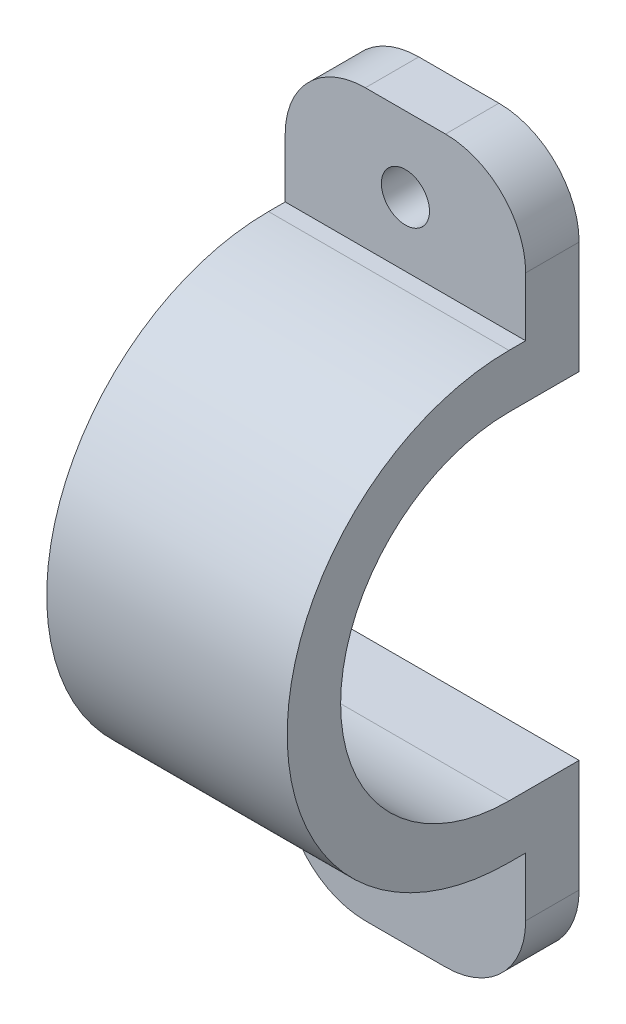
SolidWorks part; units mm, degrees
ref_plane "Top" through (0, 0, 0) normal (0, 0, 1) x (1, 0, 0)
ref_plane "Front" through (0, 0, 0) normal (0, 1, 0) x (1, 0, 0)
ref_plane "Right" through (0, 0, 0) normal (1, 0, 0) x (0, 0, -1)
sketch "Motor Clamp Sketch" plane through (0, 0, 0) normal (1, 0, 0) x (0, 0, -1)
  line L0 (-3.75, -12.6) -> (-3.75, 10.6262) construction
  line L1 (-17.75, -16.6) -> (-17.75, 16.6) construction
  line L2 (-17.75, -16.6) -> (-16.5, -16.6)
  line L3 (-16.5, -16.6) -> (-16.5, -27)
  line L4 (-16.5, -27) -> (-12.5, -27)
  line L5 (-12.5, -27) -> (-12.5, -12.6)
  line L6 (-12.5, -12.6) -> (-17.75, -12.6)
  line L7 (-17.75, 0) -> (0, 0) construction
  line L8 (-16.5, 27) -> (-12.5, 27)
  line L9 (-12.5, 12.6) -> (-17.75, 12.6)
  line L10 (-17.75, 16.6) -> (-16.5, 16.6)
  line L11 (-16.5, 16.6) -> (-16.5, 27)
  line L12 (-12.5, 27) -> (-12.5, 12.6)
  line L13 (-12, -27) -> (-12, 27) construction
  line L14 (-16.5, -16.6) -> (-16.5, -12.6) construction
  arc A0 (-17.75, 12.6) -> (-17.75, -12.6) centre (-17.75, 0) ccw
  arc A1 (-17.75, -16.6) -> (-17.75, 16.6) centre (-17.75, 0) cw
  dimension "D3" = 12.6
  dimension "Bottom Offset" = 3.75
  dimension "Center of Pump" = 14
  dimension "D1" = 4
  dimension "D2" = 27
  dimension "D4" = 0.5
  dimension "Cradle Height" = 12
extrude "Motor Clamp Extrude" add sketch "Motor Clamp Sketch" along normal blind 18 separate body
hole_wizard "Clamp Mounting Hole" positions "Clamp Mounting Hole Position Sketch" profile "Clamp Mounting Hole Profile Sketch" hole size "M3" standard "ANSI Metric" end condition up to next
sketch "Clamp Mounting Hole Position Sketch" plane through (0, 0, 16.5) normal (0, 0, 1) x (1, 0, 0)
  line L5 (0, -21.4) -> (18, -21.4) construction
  line L6 (0, -27) -> (0, -16.6) construction
  line L7 (18, -16.6) -> (18, -27) construction
  point P0 (9, -21.4)
  dimension "Screw Position" = 21.4
sketch "Clamp Mounting Hole Profile Sketch" plane through (9, -21.4, 16.5) normal (1, 0, 0) x (0, -1, 0)
  line L0 (0, 0) -> (0, 4)
  line L1 (0, 4) -> (1.8, 4)
  line L2 (1.8, 4) -> (1.8, 0)
  line L5 (1.8, 0) -> (0, 0)
  line L11 (0, -6.35) -> (0, 107.95) construction
  dimension "Thru Hole Dia." = 3.6
  dimension "Thru Hole Depth" = 4
mirror "Clamp Hole Mirro" about plane through (0, 0, 0) normal (0, 1, 0) of "Clamp Mounting Hole"
fillet "Clamp Corner Fillets" radius 6 4 edges at (18, 27, 14.5) (0, 27, 14.5) (0, -27, 14.5) (18, -27, 14.5)
equation "\"Clearance\"= 0.5mm"
equation "\"D2@Motor Clamp Sketch\"=\"Clamp Width\" / 2 "
equation "\"D4@Motor Clamp Sketch\" = \"Clearance\""
